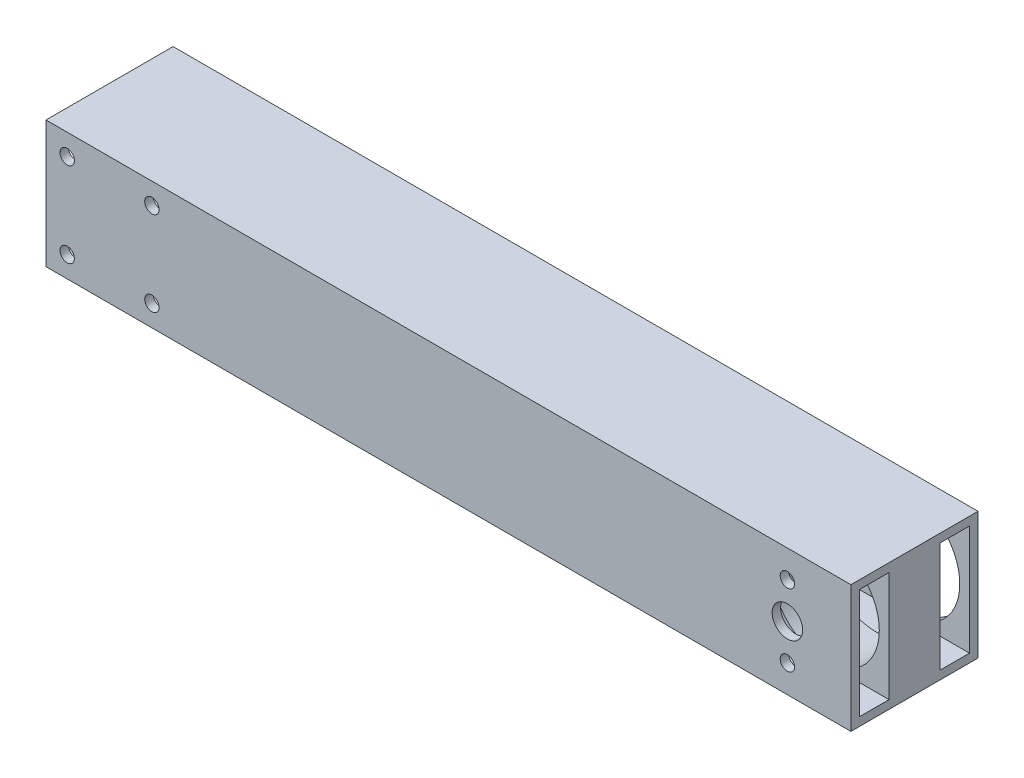
SolidWorks part; units mm, degrees
material "PLA 15%"
ref_plane "Front Plane" through (0, 0, 0) normal (0, 0, 1) x (1, 0, 0)
ref_plane "Top Plane" through (0, 0, 0) normal (0, 1, 0) x (1, 0, 0)
ref_plane "Right Plane" through (0, 0, 0) normal (1, 0, 0) x (0, 0, -1)
sketch "Sketch1" plane through (0, 0, 0) normal (1, 0, 0) x (0, 0, -1)
  line L1 (-15, -15) -> (15, -15)
  line L2 (-15, -15) -> (-15, 15)
  line L3 (-15, 15) -> (15, 15)
  line L4 (15, -15) -> (15, 15)
  line L5 (-15, -15) -> (15, 15) construction
  line L6 (-15, 15) -> (15, -15) construction
  line L11 (-5.1844, 5.1844) -> (5.1844, -5.1844) construction
  line L12 (-5.1844, -5.1844) -> (5.1844, 5.1844) construction
  line L13 (-13, 13) -> (-6, 13)
  line L14 (-13, 13) -> (-13, -13)
  line L15 (-13, -13) -> (-6, -13)
  line L16 (-6, 13) -> (-6, -13)
  line L17 (13, 13) -> (6, 13)
  line L18 (13, 13) -> (13, -13)
  line L19 (13, -13) -> (6, -13)
  line L20 (6, 13) -> (6, -13)
  point P0 (0, 0)
  point P7 (0, 0)
  dimension "D1" = 30
  dimension "D2" = 30
  dimension "D3" = 2
  dimension "D4" = 7
  dimension "D5" = 2
  dimension "D6" = 7
  dimension "D7" = 2
  dimension "D8" = 2
extrude "Boss-Extrude3" add sketch "Sketch1" along normal blind 110 and the other way blind 80
sketch "Sketch6" plane through (0, 0, -15) normal (0, 0, -1) x (-1, 0, 0)
  line L0 (-110, -15) -> (-110, 15) construction
  line L2 (-110, 0) -> (80, 0) construction
  line L3 (80, -15) -> (80, 15) construction
  circle A0 centre (-95, 0) radius 12.7
  dimension "D2" = 25.4
  dimension "D1" = 15
extrude "Cut-Extrude5" cut sketch "Sketch6" against normal blind 23
sketch "Sketch8" plane through (0, 0, 15) normal (0, 0, 1) x (1, 0, 0)
  line L0 (110, 15) -> (110, -15) construction
  circle A0 centre (95, 0) radius 3.6
  circle A1 centre (95, 8.5) radius 1.7
  circle A2 centre (95, -8.5) radius 1.7
  dimension "D2" = 7.2
  dimension "D5" = 3.4
  dimension "D1" = 15
  dimension "D3" = 8.5
  dimension "D4" = 8.5
extrude "Cut-Extrude6" cut sketch "Sketch8" against normal blind 17
sketch "Sketch9" plane through (-80, 0, 0) normal (-1, 0, 0) x (0, 0, 1)
  line L0 (-6, 13) -> (6, 13)
  line L1 (-6, -13) -> (6, -13)
  line L2 (-6, 13) -> (-6, -13)
  line L3 (6, 13) -> (6, -13)
extrude "Cut-Extrude7" cut sketch "Sketch9" against normal blind 155
sketch "Sketch13" plane through (0, 0, 15) normal (0, 0, 1) x (1, 0, 0)
  line L4 (-55, 10) -> (-55, -10) construction
  line L8 (-75, -10) -> (105, -10)
  line L9 (105, -10) -> (105, 10)
  line L10 (105, 10) -> (-75, 10)
  line L11 (-75, 10) -> (-75, -10)
  line L12 (-75, -10) -> (-55, -10) construction
  line L14 (-55, 10) -> (-75, 10) construction
  line L15 (-75, 10) -> (-75, -10) construction
  point P6 (-75, -10)
  point P8 (-55, -10)
  point P10 (-55, 10)
  point P11 (-75, 10)
  dimension "D1" = 5
hole_wizard "M3 Clearance Hole1" positions "Sketch13" profile "Sketch14" hole size "M3" standard "ANSI Metric" end condition through all
sketch "Sketch14" plane through (-75, 10, 15) normal (1, 0, 0) x (0, -1, 0)
  line L0 (0, 0) -> (0, 30)
  line L1 (0, 30) -> (1.7, 30)
  line L2 (1.7, 30) -> (1.7, 0)
  line L5 (1.7, 0) -> (0, 0)
  line L11 (0, -6.35) -> (0, 107.95) construction
  dimension "Thru Hole Dia." = 3.4
  dimension "Thru Hole Depth" = 30
